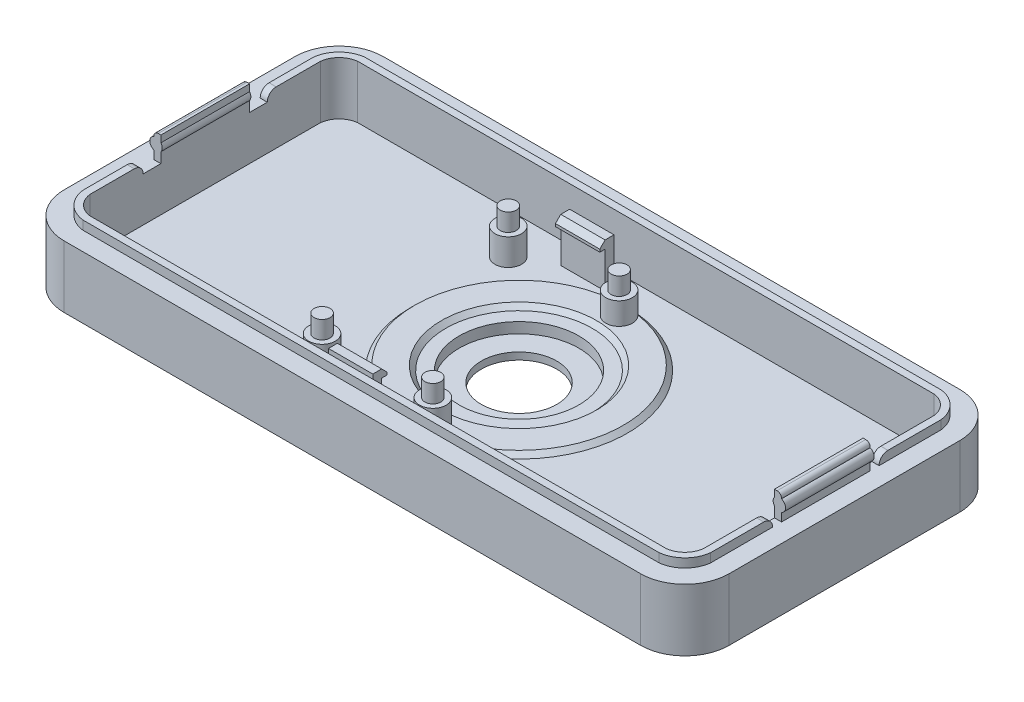
SolidWorks part; units mm, degrees
ref_plane "前视基准面" through (0, 0, 0) normal (0, 0, 1) x (1, 0, 0)
ref_plane "上视基准面" through (0, 0, 0) normal (0, 1, 0) x (1, 0, 0)
ref_plane "右视基准面" through (0, 0, 0) normal (1, 0, 0) x (0, 0, -1)
sketch "zero" plane through (0, 0, 0) normal (0, 1, 0) x (1, 0, 0)
  line L1 (-29.5, 15) -> (29.5, 15)
  line L2 (-32.5, 12) -> (-32.5, -12)
  line L3 (-29.5, -15) -> (29.5, -15)
  line L4 (32.5, 12) -> (32.5, -12)
  line L5 (-32.5, 15) -> (32.5, -15) construction
  line L6 (-32.5, -15) -> (32.5, 15) construction
  line L7 (-25.7, -15) -> (-14.5, -15)
  line L8 (-25.7, -15) -> (-25.7, -9.6569)
  line L9 (-25.7, -9.6569) -> (-14.5, -9.6569)
  line L10 (-14.5, -15) -> (-14.5, -9.6569)
  line L11 (5.2, -15) -> (12.7, -15)
  line L12 (5.2, -15) -> (5.2, -11)
  line L13 (5.2, -11) -> (12.7, -11)
  line L14 (12.7, -15) -> (12.7, -11)
  line L15 (17.8, -15) -> (25.3, -15)
  line L16 (17.8, -15) -> (17.8, -11)
  line L17 (17.8, -11) -> (25.3, -11)
  line L18 (25.3, -15) -> (25.3, -11)
  line L19 (-32.5, 7.7) -> (-19.5, 7.7)
  line L20 (-32.5, 7.7) -> (-32.5, -4.3)
  line L21 (-32.5, -4.3) -> (-19.5, -4.3)
  line L22 (-19.5, 7.7) -> (-19.5, -4.3)
  line L23 (-25.5, 14) -> (25.5, 14)
  line L24 (-25.5, 14) -> (-25.5, 8.8)
  line L25 (-25.5, 8.8) -> (25.5, 8.8)
  line L26 (25.5, 14) -> (25.5, 8.8)
  line L27 (-19.5, 7.2329) -> (-35.5, 7.2329)
  line L28 (-19.5, 7.2329) -> (-19.5, -3.7671)
  line L29 (-19.5, -3.7671) -> (-35.5, -3.7671)
  line L30 (-35.5, 7.2329) -> (-35.5, -3.7671)
  arc A0 (29.5, -15) -> (32.5, -12) centre (29.5, -12) ccw
  arc A1 (29.5, 15) -> (32.5, 12) centre (29.5, 12) cw
  arc A2 (-32.5, -12) -> (-29.5, -15) centre (-29.5, -12) ccw
  arc A3 (-29.5, 15) -> (-32.5, 12) centre (-29.5, 12) ccw
  circle A4 centre (-29, 11.4) radius 3
  circle A5 centre (-29, -11.5) radius 3
  circle A6 centre (29, 11.4) radius 3
  circle A7 centre (29, -11.5) radius 3
  circle A8 centre (-29, 11.4) radius 1.375
  circle A9 centre (-29, -11.5) radius 1.375
  circle A10 centre (29, -11.5) radius 1.375
  circle A11 centre (29, 11.4) radius 1.375
  point P0 (0, 0)
  dimension "D3" = 3
  dimension "D4" = 6
  dimension "D9" = 2.75
  dimension "D1" = 65
  dimension "D2" = 30
  dimension "D5" = 3.6
  dimension "D6" = 3.5
  dimension "D7" = 3.5
  dimension "D8" = 3.5
  dimension "D10" = 12
  dimension "D11" = 7.3
  dimension "D12" = 13
  dimension "D13" = 11.2
  dimension "D14" = 6.8
  dimension "D15" = 19.7
  dimension "D16" = 7.5
  dimension "D17" = 7.5
  dimension "D18" = 5.1
  dimension "D19" = 4
  dimension "D20" = 5.2
  dimension "D21" = 7
  dimension "D22" = 7
  dimension "D23" = 1
  dimension "D24" = 11
  dimension "D25" = 16
sketch "sugar" plane through (0, 0, 0) normal (0, 1, 0) x (1, 0, 0)
  line L1 (-29.5, 15) -> (29.5, 15)
  line L2 (-32.5, 12) -> (-32.5, -12)
  line L3 (-29.5, -15) -> (29.5, -15)
  line L4 (32.5, 12) -> (32.5, -12)
  line L5 (-32.5, 15) -> (32.5, -15) construction
  line L6 (-32.5, -15) -> (32.5, 15) construction
  line L7 (23.5, -11.5) -> (19.5, -11.5)
  line L8 (23.5, -11.5) -> (23.5, -13.9082)
  line L9 (23.5, -13.9082) -> (19.5, -13.9082)
  line L10 (19.5, -11.5) -> (19.5, -13.9082)
  line L11 (16, -11.0071) -> (8.5, -11.0071)
  line L12 (16, -11.0071) -> (16, -15)
  line L13 (16, -15) -> (8.5, -15)
  line L14 (8.5, -11.0071) -> (8.5, -15)
  line L15 (20.5, -13.9082) -> (22.5, -13.9082)
  line L16 (20.5, -13.9082) -> (20.5, -14.8173)
  line L17 (20.5, -14.8173) -> (22.5, -14.8173)
  line L18 (22.5, -13.9082) -> (22.5, -14.8173)
  arc A0 (29.5, 15) -> (32.5, 12) centre (29.5, 12) cw
  arc A1 (29.5, -15) -> (32.5, -12) centre (29.5, -12) ccw
  arc A2 (-32.5, -12) -> (-29.5, -15) centre (-29.5, -12) ccw
  arc A3 (-29.5, 15) -> (-32.5, 12) centre (-29.5, 12) ccw
  circle A4 centre (-29, 11.4) radius 3
  circle A5 centre (-29, 11.4) radius 1.375
  circle A6 centre (-29, -11.5) radius 3
  circle A7 centre (-29, -11.5) radius 1.375
  circle A8 centre (29, 11.4) radius 3
  circle A9 centre (29, 11.4) radius 1.375
  circle A10 centre (29, -11.5) radius 3
  circle A11 centre (29, -11.5) radius 1.375
  dimension "D3" = 3
  dimension "D1" = 65
  dimension "D2" = 30
  dimension "D4" = 9
  dimension "D5" = 4
  dimension "D6" = 3.5
  dimension "D7" = 7.5
  dimension "D8" = 2
  dimension "D9" = 1
sketch "case" plane through (0, 0, 0) normal (0, 1, 0) x (1, 0, 0)
  line L1 (-34.0422, 18) -> (30.9578, 18)
  line L2 (-39.0422, 13) -> (-39.0422, -13)
  line L3 (-34.0422, -18) -> (30.9578, -18)
  line L4 (35.9578, 13) -> (35.9578, -13)
  line L5 (-39.0422, 18) -> (35.9578, -18) construction
  line L6 (-39.0422, -18) -> (35.9578, 18) construction
  arc A0 (-39.0422, -13) -> (-34.0422, -18) centre (-34.0422, -13) ccw
  arc A1 (30.9578, -18) -> (35.9578, -13) centre (30.9578, -13) ccw
  arc A2 (30.9578, 18) -> (35.9578, 13) centre (30.9578, 13) cw
  arc A3 (-34.0422, 18) -> (-39.0422, 13) centre (-34.0422, 13) ccw
  point P0 (-1.5422, 0)
  point P3 (-1.5422, 0)
  dimension "D3" = 5
  dimension "D1" = 75
  dimension "D2" = 36
extrude "凸台-拉伸2" add sketch "case" along normal blind 7
sketch "草图2" plane through (0, 0, 0) normal (0, 1, 0) x (1, 0, 0)
  line L4 (-34.0422, -15.1) -> (30.9578, -15.1)
  line L5 (33.0578, -13) -> (33.0578, 13)
  line L6 (30.9578, 15.1) -> (-34.0422, 15.1)
  line L7 (-36.1422, 13) -> (-36.1422, -13)
  line L12 (33.8578, -13) -> (33.8578, 13)
  line L13 (30.9578, 15.9) -> (-34.0422, 15.9)
  line L14 (-36.9422, 13) -> (-36.9422, -13)
  line L15 (-34.0422, -15.9) -> (30.9578, -15.9)
  arc A4 (30.9578, -15.1) -> (33.0578, -13) centre (30.6746, -12.7168) ccw
  arc A5 (33.0578, 13) -> (30.9578, 15.1) centre (30.6746, 12.7168) ccw
  arc A6 (-34.0422, 15.1) -> (-36.1422, 13) centre (-33.759, 12.7168) ccw
  arc A7 (-36.1422, -13) -> (-34.0422, -15.1) centre (-33.759, -12.7168) ccw
  arc A12 (30.9578, -15.9) -> (33.8578, -13) centre (30.5796, -12.6217) ccw
  arc A13 (33.8578, 13) -> (30.9578, 15.9) centre (30.5796, 12.6217) ccw
  arc A14 (-34.0422, 15.9) -> (-36.9422, 13) centre (-33.6639, 12.6217) ccw
  arc A15 (-36.9422, -13) -> (-34.0422, -15.9) centre (-33.6639, -12.6217) ccw
ref_plane "基准面1" through (0, 7, 0) normal (0, 1, 0) x (1, 0, 0)
sketch "草图3" plane through (0, 7, 0) normal (0, 1, 0) x (1, 0, 0)
  line L4 (-34.0422, -15.1) -> (30.9578, -15.1)
  line L5 (33.0578, -13) -> (33.0578, 13)
  line L6 (30.9578, 15.1) -> (-34.0422, 15.1)
  line L7 (-36.1422, 13) -> (-36.1422, -13)
  line L8 (-34.0422, -15.1) -> (30.9578, -15.1)
  line L9 (33.0578, -13) -> (33.0578, 13)
  line L10 (30.9578, 15.1) -> (-34.0422, 15.1)
  line L11 (-36.1422, 13) -> (-36.1422, -13)
  line L12 (-36.9422, 13) -> (-36.9422, -13)
  line L13 (-34.0422, -15.9) -> (30.9578, -15.9)
  line L14 (33.8578, -13) -> (33.8578, 13)
  line L15 (30.9578, 15.9) -> (-34.0422, 15.9)
  line L16 (-36.9422, 13) -> (-36.9422, -13)
  line L17 (-34.0422, -15.9) -> (30.9578, -15.9)
  line L18 (33.8578, -13) -> (33.8578, 13)
  line L19 (30.9578, 15.9) -> (-34.0422, 15.9)
  arc A4 (30.9578, -15.1) -> (33.0578, -13) centre (30.6746, -12.7168) ccw
  arc A5 (33.0578, 13) -> (30.9578, 15.1) centre (30.6746, 12.7168) ccw
  arc A6 (-34.0422, 15.1) -> (-36.1422, 13) centre (-33.759, 12.7168) ccw
  arc A7 (-36.1422, -13) -> (-34.0422, -15.1) centre (-33.759, -12.7168) ccw
  arc A8 (30.9578, -15.1) -> (33.0578, -13) centre (30.6746, -12.7168) ccw
  arc A9 (33.0578, 13) -> (30.9578, 15.1) centre (30.6746, 12.7168) ccw
  arc A10 (-34.0422, 15.1) -> (-36.1422, 13) centre (-33.759, 12.7168) ccw
  arc A11 (-36.1422, -13) -> (-34.0422, -15.1) centre (-33.759, -12.7168) ccw
  arc A12 (-36.9422, -13) -> (-34.0422, -15.9) centre (-33.6639, -12.6217) ccw
  arc A13 (30.9578, -15.9) -> (33.8578, -13) centre (30.5796, -12.6217) ccw
  arc A14 (33.8578, 13) -> (30.9578, 15.9) centre (30.5796, 12.6217) ccw
  arc A15 (-34.0422, 15.9) -> (-36.9422, 13) centre (-33.6639, 12.6217) ccw
  arc A16 (-36.9422, -13) -> (-34.0422, -15.9) centre (-33.6639, -12.6217) ccw
  arc A17 (30.9578, -15.9) -> (33.8578, -13) centre (30.5796, -12.6217) ccw
  arc A18 (33.8578, 13) -> (30.9578, 15.9) centre (30.5796, 12.6217) ccw
  arc A19 (-34.0422, 15.9) -> (-36.9422, 13) centre (-33.6639, 12.6217) ccw
  dimension "D1" = 0
  dimension "D2" = 0
extrude "凸台-拉伸4" add sketch "草图3" along normal blind 1
ref_plane "基准面3" through (33.8578, 0, 0) normal (1, 0, 0) x (0, 0, -1)
sketch "草图7" plane through (0, 7, 0) normal (0, 1, 0) x (1, 0, 0)
  line L0 (-36.9422, 13) -> (-36.9422, -13) construction
  line L1 (-36.9422, 5) -> (-36.1422, 5)
  line L2 (-36.9422, 5) -> (-36.9422, -5)
  line L3 (-36.9422, -5) -> (-36.1422, -5)
  line L4 (-36.1422, 5) -> (-36.1422, -5)
  line L5 (-36.1422, 13) -> (-36.1422, -13) construction
  point P10 (-36.1422, 0)
  dimension "D1" = 5
  dimension "D2" = 10
extrude "凸台-拉伸8" add sketch "草图7" along normal blind 2.8
ref_plane "基准面5" through (0, 0, 5) normal (0, 0, 1) x (1, 0, 0)
sketch "草图8" plane through (0, 0, 5) normal (0, 0, 1) x (1, 0, 0)
  line L0 (-34.0422, 7) -> (-39.0422, 7) construction
  line L1 (-36.9422, 9.8) -> (-36.9422, 8) construction
  circle A0 centre (-36.6922, 8.6) radius 0.7
  dimension "D1" = 1.4
  dimension "D2" = 1.6
  dimension "D3" = 0.25
extrude "凸台-拉伸9" add sketch "草图8" against normal blind 10
fillet "圆角3" radius 0.5 1 edges at (-36.9422, 9.8, 0)
sketch "草图13" plane through (0, 8, 0) normal (0, 1, 0) x (1, 0, 0)
  line L0 (-36.9422, -5) -> (-36.9422, -13) construction
  line L1 (-36.1422, -5) -> (-36.9422, -5)
  line L2 (-36.1422, -5) -> (-36.1422, -7)
  line L3 (-36.1422, -7) -> (-36.9422, -7)
  line L4 (-36.9422, -5) -> (-36.9422, -7)
  line L5 (-36.9422, 13) -> (-36.9422, 5) construction
  line L6 (-36.1422, 5) -> (-36.9422, 5)
  line L7 (-36.1422, 5) -> (-36.1422, 7)
  line L8 (-36.1422, 7) -> (-36.9422, 7)
  line L9 (-36.9422, 5) -> (-36.9422, 7)
  dimension "D1" = 2
  dimension "D2" = 2
extrude "切除-拉伸2" cut sketch "草图13" against normal blind 1
sketch "草图15" plane through (0, 7, 0) normal (0, 1, 0) x (1, 0, 0)
  line L4 (-34.0422, -15.1) -> (30.9578, -15.1)
  line L5 (33.0578, -13) -> (33.0578, 13)
  line L6 (30.9578, 15.1) -> (-34.0422, 15.1)
  line L7 (-36.1422, 13) -> (-36.1422, -13)
  line L8 (-34.0422, -15.1) -> (30.9578, -15.1)
  line L9 (33.0578, -13) -> (33.0578, 13)
  line L10 (30.9578, 15.1) -> (-34.0422, 15.1)
  line L11 (-36.1422, 13) -> (-36.1422, -13)
  arc A4 (30.9578, -15.1) -> (33.0578, -13) centre (30.6746, -12.7168) ccw
  arc A5 (33.0578, 13) -> (30.9578, 15.1) centre (30.6746, 12.7168) ccw
  arc A6 (-34.0422, 15.1) -> (-36.1422, 13) centre (-33.759, 12.7168) ccw
  arc A7 (-36.1422, -13) -> (-34.0422, -15.1) centre (-33.759, -12.7168) ccw
  arc A8 (30.9578, -15.1) -> (33.0578, -13) centre (30.6746, -12.7168) ccw
  arc A9 (33.0578, 13) -> (30.9578, 15.1) centre (30.6746, 12.7168) ccw
  arc A10 (-34.0422, 15.1) -> (-36.1422, 13) centre (-33.759, 12.7168) ccw
  arc A11 (-36.1422, -13) -> (-34.0422, -15.1) centre (-33.759, -12.7168) ccw
  dimension "D1" = 0
extrude "切除-拉伸3" cut sketch "草图15" against normal blind 5
sketch "草图19" plane through (0, 2, 0) normal (0, 1, 0) x (1, 0, 0)
  line L1 (-39.0422, 13) -> (-39.0422, -13) construction
  circle A0 centre (-0.75, 0) radius 4.25
  dimension "D1" = 8.5
  dimension "D2" = 38.2922
extrude "切除-拉伸4" cut sketch "草图19" against normal blind 3
sketch "草图21" plane through (0, 2, 0) normal (0, 1, 0) x (1, 0, 0)
  line L0 (-34.0422, -15.1) -> (30.9578, -15.1) construction
  line L1 (30.9578, 15.1) -> (-34.0422, 15.1) construction
  line L3 (-36.1422, -7) -> (-36.1422, -13) construction
  line L4 (-36.1422, 13) -> (-36.1422, -13) construction
  line L5 (30.9578, 15.1) -> (-34.0422, 15.1) construction
  line L6 (-34.0422, -15.1) -> (30.9578, -15.1) construction
  circle A0 centre (-12.4653, 10.5) radius 1.5
  circle A1 centre (0.0347, 10.5) radius 1.5
  circle A2 centre (-12.4653, -10.5) radius 1.5
  circle A3 centre (0.0347, -10.5) radius 1.5
  dimension "D1" = 3
  dimension "D2" = 12.5
  dimension "D3" = 12.5
  dimension "D4" = 4.6
  dimension "D5" = 4.6
  dimension "D6" = 23.6769
  dimension "D7" = 23.6769
  dimension "D8" = 4.6
  dimension "D9" = 4.6
extrude "凸台-拉伸11" add sketch "草图21" along normal blind 3
sketch "草图22" plane through (0, 5, 0) normal (0, 1, 0) x (1, 0, 0)
  circle A0 centre (-12.4653, -10.5) radius 0.9
  circle A1 centre (0.0347, -10.5) radius 0.9
  circle A2 centre (-12.4653, 10.5) radius 0.9
  circle A3 centre (0.0347, 10.5) radius 0.9
  circle A4 centre (-12.4653, 10.5) radius 1.5 construction
  circle A5 centre (-12.4653, -10.5) radius 1.5 construction
  circle A6 centre (0.0347, -10.5) radius 1.5 construction
  circle A7 centre (0.0347, 10.5) radius 1.5 construction
  dimension "D1" = 1.8
extrude "凸台-拉伸12" add sketch "草图22" along normal blind 2
sketch "草图28" plane through (0, 2, 0) normal (0, 1, 0) x (1, 0, 0)
  line L0 (30.9578, 15.1) -> (-34.0422, 15.1) construction
  line L1 (-3.6422, -12.6) -> (-8.6422, -12.6)
  line L2 (-3.6422, -12.6) -> (-3.6422, -13.6)
  line L3 (-3.6422, -13.6) -> (-8.6422, -13.6)
  line L4 (-8.6422, -12.6) -> (-8.6422, -13.6)
  line L5 (-3.6422, 13.6) -> (-8.6422, 13.6)
  line L6 (-3.6422, 13.6) -> (-3.6422, 12.6)
  line L7 (-3.6422, 12.6) -> (-8.6422, 12.6)
  line L8 (-8.6422, 13.6) -> (-8.6422, 12.6)
  line L9 (-34.0422, -15.1) -> (30.9578, -15.1) construction
  line L10 (-36.1422, -7) -> (-36.1422, -13) construction
  dimension "D1" = 1
  dimension "D2" = 1.5
  dimension "D3" = 5
  dimension "D4" = 1.5
  dimension "D5" = 27.5
extrude "凸台-拉伸16" add sketch "草图28" along normal blind 5
fillet "圆角4" radius 1 2 edges at (-6.1422, 2, -13.6) (-6.1422, 2, 13.6)
sketch "草图29" plane through (0, 0, 12.6) normal (0, 0, -1) x (-1, 0, 0)
  line L0 (8.6422, 7) -> (8.6422, 2) construction
  line L1 (3.6422, 7) -> (8.6422, 7)
  line L2 (3.6422, 7) -> (3.6422, 6.1)
  line L3 (3.6422, 6.1) -> (8.6422, 6.1)
  line L4 (8.6422, 7) -> (8.6422, 6.1)
  dimension "D1" = 0.9
extrude "凸台-拉伸17" add sketch "草图29" along normal blind 0.6
sketch "草图30" plane through (0, 0, -12.6) normal (0, 0, 1) x (1, 0, 0)
  line L0 (-3.6422, 7) -> (-3.6422, 2) construction
  line L1 (-8.6422, 7) -> (-3.6422, 7)
  line L2 (-8.6422, 7) -> (-8.6422, 6.1)
  line L3 (-8.6422, 6.1) -> (-3.6422, 6.1)
  line L4 (-3.6422, 7) -> (-3.6422, 6.1)
  dimension "D1" = 0.9
extrude "凸台-拉伸18" add sketch "草图30" along normal blind 0.6
chamfer "倒角5" distance 0.6 angle 45 2 edges at (-6.1422, 7, -12) (-6.1422, 7, 12)
sketch "草图32" plane through (0, 0, 0) normal (0, 1, 0) x (1, 0, 0)
  line L75 (-14.6761, -9.5363) -> (-15.4836, -9.6938)
  line L76 (-12.4748, -8.5613) -> (-14.1869, -8.5613)
  line L77 (-12.4748, -7.6298) -> (-12.4748, -8.5613)
  line L78 (-15.4702, -7.6298) -> (-12.4748, -7.6298)
  line L79 (-15.4702, -8.3938) -> (-15.4702, -7.6298)
  line L80 (-14.9509, -8.4574) -> (-15.4702, -8.3938)
  line L81 (-14.9509, -8.4776) -> (-14.9509, -8.4574)
  line L82 (-13.8452, -6.0752) -> (-13.366, -6.0752)
  line L83 (-12.4748, -7.0133) -> (-14.1769, -7.0133)
  line L84 (-12.4748, -6.2494) -> (-12.4748, -7.0133)
  line L85 (-12.7763, -6.1824) -> (-12.4748, -6.2494)
  line L86 (-12.7763, -6.1589) -> (-12.7763, -6.1824)
  line L87 (-15.1519, -4.5104) -> (-14.5354, -4.8388)
  line L88 (-12.3475, -2.6743) -> (-12.3475, -2.9592)
  line L89 (-12.5853, -1.763) -> (-12.5586, -1.763)
  line L90 (-13.681, -1.8199) -> (-13.6609, -1.8199)
  line L91 (-15.4702, -4.2424) -> (-15.4702, -3.1434)
  line L92 (-14.7934, -4.2424) -> (-15.4702, -4.2424)
  line L93 (-14.7934, -3.78) -> (-14.7934, -4.2424)
  line L94 (-13.0645, -3.1367) -> (-13.0645, -2.6643)
  line L95 (-15.4702, -0.8717) -> (-15.4702, 0.0664)
  line L96 (-12.4748, -0.8717) -> (-15.4702, -0.8717)
  line L97 (-12.4748, -0.1078) -> (-12.4748, -0.8717)
  line L98 (-12.8869, -0.0408) -> (-12.4748, -0.1078)
  line L99 (-12.8869, -0.0207) -> (-12.8869, -0.0408)
  line L100 (-15.4702, 1.849) -> (-13.6173, 1.849)
  line L101 (-15.4702, 0.9141) -> (-15.4702, 1.849)
  line L102 (-13.7346, 0.9141) -> (-15.4702, 0.9141)
  line L103 (-15.4702, 0.0664) -> (-13.5068, 0.0664)
  line L104 (-13.614, 4.7204) -> (-12.964, 5.2531)
  line L105 (-14.207, 4.3083) -> (-13.9959, 3.809)
  line L106 (-15.3596, 2.8776) -> (-15.9493, 2.4085)
  line L107 (-14.7029, 3.0686) -> (-14.8973, 3.5577)
  line L108 (-15.3362, 5.8361) -> (-15.3362, 6.3153)
  line L109 (-12.4748, 5.8361) -> (-15.3362, 5.8361)
  line L110 (-12.4748, 6.3153) -> (-12.4748, 5.8361)
  line L111 (-15.3362, 6.3153) -> (-12.4748, 6.3153)
  line L112 (-15.9393, 9.0091) -> (-15.9393, 8.4529)
  line L113 (-14.4014, 9.0091) -> (-15.9393, 9.0091)
  line L114 (-14.4014, 8.4328) -> (-14.4014, 9.0091)
  line L115 (-14.006, 9.0091) -> (-14.006, 8.3692)
  line L116 (-12.4748, 9.0091) -> (-14.006, 9.0091)
  line L117 (-12.4748, 9.4984) -> (-12.4748, 9.0091)
  line L118 (-16.3346, 9.4984) -> (-12.4748, 9.4984)
  line L119 (-16.3346, 8.396) -> (-16.3346, 9.4984)
  spline S0 degree 3 poles (-15.4836, -9.6938) (-15.5205, -9.61) (-15.5439, -9.5095) (-15.5439, -9.3319) knots 10 10 10 10 11 11 11 11
  spline S1 degree 3 poles (-14.723, -9.208) (-14.723, -9.342) (-14.7029, -9.4291) (-14.6761, -9.5363) knots 8 8 8 8 9 9 9 9
  spline S2 degree 3 poles (-14.1869, -8.5613) (-14.5823, -8.7188) (-14.723, -8.9869) (-14.723, -9.208) knots 7 7 7 7 8 8 8 8
  spline S3 degree 3 poles (-15.5439, -9.3319) (-15.5439, -9.0304) (-15.3496, -8.6987) (-14.9509, -8.4776) knots 0 0 0 0 1 1 1 1
  spline S4 degree 3 poles (-13.3861, -5.3012) (-13.5972, -5.3012) (-13.7648, -5.4922) (-13.8452, -6.0752) knots 2 2 2 2 3 3 3 3
  spline S5 degree 3 poles (-13.1282, -5.6229) (-13.1282, -5.4285) (-13.2119, -5.3012) (-13.3861, -5.3012) knots 1 1 1 1 2 2 2 2
  spline S6 degree 3 poles (-13.366, -6.0752) (-13.2186, -5.9378) (-13.1282, -5.8138) (-13.1282, -5.6229) knots 0 0 0 0 1 1 1 1
  spline S7 degree 3 poles (-14.1769, -7.0133) (-15.1151, -7.0133) (-15.5439, -6.5744) (-15.5439, -5.8004) knots 11 11 11 11 12 12 12 12
  spline S8 degree 3 poles (-12.4011, -5.3012) (-12.4011, -5.6329) (-12.5552, -5.911) (-12.7763, -6.1589) knots 6 6 6 6 7 7 7 7
  spline S9 degree 3 poles (-13.3124, -4.4099) (-12.8132, -4.4099) (-12.4011, -4.7483) (-12.4011, -5.3012) knots 5 5 5 5 6 6 6 6
  spline S10 degree 3 poles (-14.4148, -6.0752) (-14.2874, -4.9058) (-13.9457, -4.4099) (-13.3124, -4.4099) knots 4 4 4 4 5 5 5 5
  spline S11 degree 3 poles (-14.7967, -5.6229) (-14.7967, -5.9277) (-14.656, -6.0551) (-14.4148, -6.0752) knots 3 3 3 3 4 4 4 4
  spline S12 degree 3 poles (-14.5354, -4.8388) (-14.7029, -5.137) (-14.7967, -5.385) (-14.7967, -5.6229) knots 2 2 2 2 3 3 3 3
  spline S13 degree 3 poles (-15.5439, -5.8004) (-15.5439, -5.3347) (-15.3864, -4.9058) (-15.1519, -4.5104) knots 0 0 0 0 1 1 1 1
  spline S14 degree 3 poles (-12.133, -3.3947) (-11.942, -3.3947) (-11.8013, -3.1267) (-11.8013, -2.7413) knots 5 5 5 5 6 6 6 6
  spline S15 degree 3 poles (-12.3475, -2.9592) (-12.3475, -3.2372) (-12.3106, -3.3947) (-12.133, -3.3947) knots 4 4 4 4 5 5 5 5
  spline S16 degree 3 poles (-12.3843, -2.2454) (-12.3575, -2.3426) (-12.3475, -2.4566) (-12.3475, -2.6743) knots 2 2 2 2 3 3 3 3
  spline S17 degree 3 poles (-12.1163, -2.1047) (-12.2168, -2.1047) (-12.3006, -2.1516) (-12.3843, -2.2454) knots 1 1 1 1 2 2 2 2
  spline S18 degree 3 poles (-11.8013, -2.7413) (-11.8013, -2.356) (-11.9052, -2.1047) (-12.1163, -2.1047) knots 0 0 0 0 1 1 1 1
  spline S19 degree 3 poles (-14.9174, -2.6676) (-14.9174, -2.8888) (-14.7599, -3.0462) (-14.455, -3.0462) (-14.1434, -3.0462) (-13.9859, -2.8888) (-13.9859, -2.6676) knots 0 0 0 0 1 1 1 2 2 2 2
  spline S20 degree 3 poles (-13.9859, -2.6676) (-13.9859, -2.4532) (-14.1434, -2.289) (-14.455, -2.289) (-14.7599, -2.289) (-14.9174, -2.4532) (-14.9174, -2.6676) knots 2 2 2 2 3 3 3 4 4 4 4
  spline S21 degree 3 poles (-12.2972, -4.2893) (-12.84, -4.2893) (-13.0645, -3.8739) (-13.0645, -3.1367) knots 19 19 19 19 20 20 20 20
  spline S22 degree 3 poles (-11.215, -2.5939) (-11.215, -3.6359) (-11.6639, -4.2893) (-12.2972, -4.2893) knots 18 18 18 18 19 19 19 19
  spline S23 degree 3 poles (-11.9688, -1.3374) (-11.4328, -1.3374) (-11.215, -1.9037) (-11.215, -2.5939) knots 17 17 17 17 18 18 18 18
  spline S24 degree 3 poles (-12.5586, -1.763) (-12.4178, -1.4849) (-12.2168, -1.3374) (-11.9688, -1.3374) knots 16 16 16 16 17 17 17 17
  spline S25 degree 3 poles (-13.1013, -1.4882) (-12.8501, -1.4882) (-12.6926, -1.6055) (-12.5853, -1.763) knots 14 14 14 14 15 15 15 15
  spline S26 degree 3 poles (-13.6609, -1.8199) (-13.5235, -1.6256) (-13.3124, -1.4882) (-13.1013, -1.4882) knots 13 13 13 13 14 14 14 14
  spline S27 degree 3 poles (-14.455, -1.4145) (-14.1065, -1.4145) (-13.8284, -1.6089) (-13.681, -1.8199) knots 11 11 11 11 12 12 12 12
  spline S28 degree 3 poles (-15.5439, -2.6676) (-15.5439, -2.021) (-15.1888, -1.4145) (-14.455, -1.4145) knots 10 10 10 10 11 11 11 11
  spline S86 degree 3 poles (-15.4702, -3.1434) (-15.5205, -3.006) (-15.5439, -2.8419) (-15.5439, -2.6676) knots 9 9 9 9 10 10 10 10
  spline S87 degree 3 poles (-14.4282, -3.8638) (-14.5723, -3.8638) (-14.7096, -3.8269) (-14.7934, -3.78) knots 5 5 5 5 6 6 6 6
  spline S88 degree 3 poles (-13.423, -2.6676) (-13.423, -3.331) (-13.7279, -3.8638) (-14.4282, -3.8638) knots 4 4 4 4 5 5 5 5
  spline S89 degree 3 poles (-13.4766, -2.3158) (-13.4398, -2.4465) (-13.423, -2.5671) (-13.423, -2.6676) knots 3 3 3 3 4 4 4 4
  spline S90 degree 3 poles (-13.2655, -2.222) (-13.366, -2.222) (-13.4129, -2.2454) (-13.4766, -2.3158) knots 2 2 2 2 3 3 3 3
  spline S91 degree 3 poles (-13.0645, -2.6643) (-13.0645, -2.3426) (-13.1282, -2.222) (-13.2655, -2.222) knots 1 1 1 1 2 2 2 2
  spline S92 degree 3 poles (-12.4011, 0.9175) (-12.4011, 0.5087) (-12.5921, 0.2272) (-12.8869, -0.0207) knots 7 7 7 7 8 8 8 8
  spline S93 degree 3 poles (-13.6173, 1.849) (-12.8702, 1.849) (-12.4011, 1.5708) (-12.4011, 0.9175) knots 6 6 6 6 7 7 7 7
  spline S94 degree 3 poles (-13.2019, 0.5657) (-13.2019, 0.8036) (-13.3191, 0.9141) (-13.7346, 0.9141) knots 2 2 2 2 3 3 3 3
  spline S95 degree 3 poles (-13.5068, 0.0664) (-13.2856, 0.2239) (-13.2019, 0.3546) (-13.2019, 0.5657) knots 1 1 1 1 2 2 2 2
  spline S96 degree 3 poles (-13.6274, 2.2913) (-14.1802, 2.2913) (-14.5086, 2.5827) (-14.7029, 3.0686) knots 15 15 15 15 16 16 16 16
  spline S97 degree 3 poles (-12.4011, 3.789) (-12.4011, 2.8407) (-12.974, 2.2913) (-13.6274, 2.2913) knots 14 14 14 14 15 15 15 15
  spline S98 degree 3 poles (-12.964, 5.2531) (-12.5921, 4.8477) (-12.4011, 4.2983) (-12.4011, 3.789) knots 13 13 13 13 14 14 14 14
  spline S99 degree 3 poles (-13.2119, 3.7688) (-13.2119, 4.0771) (-13.3761, 4.4423) (-13.614, 4.7204) knots 11 11 11 11 12 12 12 12
  spline S100 degree 3 poles (-13.5537, 3.2562) (-13.3426, 3.2562) (-13.2119, 3.4204) (-13.2119, 3.7688) knots 10 10 10 10 11 11 11 11
  spline S101 degree 3 poles (-13.9959, 3.809) (-13.8552, 3.474) (-13.7815, 3.2562) (-13.5537, 3.2562) knots 9 9 9 9 10 10 10 10
  spline S102 degree 3 poles (-15.2826, 5.1057) (-14.713, 5.1057) (-14.3712, 4.7204) (-14.207, 4.3083) knots 7 7 7 7 8 8 8 8
  spline S103 degree 3 poles (-16.4687, 3.6817) (-16.4687, 4.516) (-15.9393, 5.1057) (-15.2826, 5.1057) knots 6 6 6 6 7 7 7 7
  spline S104 degree 3 poles (-15.9493, 2.4085) (-16.2944, 2.7502) (-16.4687, 3.2294) (-16.4687, 3.6817) knots 5 5 5 5 6 6 6 6
  spline S105 degree 3 poles (-15.6612, 3.6817) (-15.6612, 3.3768) (-15.5573, 3.1356) (-15.3596, 2.8776) knots 3 3 3 3 4 4 4 4
  spline S106 degree 3 poles (-15.3362, 4.1508) (-15.5439, 4.1508) (-15.6612, 3.9732) (-15.6612, 3.6817) knots 2 2 2 2 3 3 3 3
  spline S107 degree 3 poles (-14.8973, 3.5577) (-15.0346, 3.9029) (-15.1184, 4.1508) (-15.3362, 4.1508) knots 1 1 1 1 2 2 2 2
  spline S108 degree 3 poles (-16.5457, 6.074) (-16.5457, 6.265) (-16.4318, 6.4057) (-16.2341, 6.4057) (-16.0566, 6.4057) (-15.9259, 6.265) (-15.9259, 6.074) knots 0 0 0 0 1 1 1 2 2 2 2
  spline S109 degree 3 poles (-15.9259, 6.074) (-15.9259, 5.8831) (-16.0566, 5.7423) (-16.2341, 5.7423) (-16.4318, 5.7423) (-16.5457, 5.8831) (-16.5457, 6.074) knots 2 2 2 2 3 3 3 4 4 4 4
  spline S110 degree 3 poles (-15.2022, 7.4343) (-14.6493, 7.4343) (-14.4014, 7.7527) (-14.4014, 8.4328) knots 4 4 4 4 5 5 5 5
  spline S111 degree 3 poles (-15.9393, 8.4529) (-15.9393, 7.7761) (-15.7617, 7.4343) (-15.2022, 7.4343) knots 3 3 3 3 4 4 4 4
  spline S112 degree 3 poles (-15.2022, 6.9485) (-16.0465, 6.9485) (-16.3346, 7.5282) (-16.3346, 8.396) knots 6 6 6 6 7 7 7 7
  spline S113 degree 3 poles (-14.006, 8.3692) (-14.006, 7.5282) (-14.388, 6.9485) (-15.2022, 6.9485) knots 5 5 5 5 6 6 6 6
sketch "草图33" plane through (0, 0, 0) normal (0, -1, 0) x (1, 0, 0)
  line L0 (31.4528, 12.8823) -> (31.1283, 13.0694)
  line L1 (31.1283, 13.0694) -> (29.4447, 14.0408)
  line L2 (29.4447, 14.0408) -> (29.1201, 14.2301)
  line L3 (28.4395, 14.2301) -> (28.1149, 14.0408)
  line L4 (28.1149, 14.0408) -> (26.4313, 13.0694)
  line L5 (26.4313, 13.0694) -> (26.1067, 12.8823)
  line L6 (25.7664, 12.2941) -> (25.7664, 9.5985)
  line L7 (26.1067, 9.0102) -> (26.4313, 8.8231)
  line L8 (26.4313, 8.8231) -> (28.1149, 7.8517)
  line L9 (28.1149, 7.8517) -> (28.4395, 7.6624)
  line L10 (29.1201, 7.6624) -> (29.4447, 7.8517)
  line L11 (29.4447, 7.8517) -> (31.1283, 8.8231)
  line L12 (31.1283, 8.8231) -> (31.4528, 9.0102)
  line L13 (31.7932, 9.5985) -> (31.7932, 12.2941)
  line L14 (26.5395, 12.6141) -> (28.622, 13.8177)
  line L15 (28.9398, 13.8177) -> (31.0111, 12.6118)
  line L16 (31.0134, 12.3346) -> (29.0007, 11.1311)
  line L17 (29.625, 9.0913) -> (29.3906, 8.9606)
  line L18 (29.368, 8.9223) -> (29.368, 8.2461)
  line L19 (29.3455, 8.2078) -> (28.9083, 7.9599)
  line L20 (28.8429, 7.9982) -> (28.8429, 10.0853)
  line L21 (28.8654, 10.1236) -> (29.6092, 10.5451)
  line L22 (31.1689, 9.2311) -> (30.7361, 8.9854)
  line L23 (30.6708, 9.0237) -> (30.6708, 10.0177)
  line L24 (30.6933, 10.056) -> (31.126, 10.2994)
  line L25 (31.1914, 10.2611) -> (31.1914, 9.2694)
  line L26 (29.5979, 9.4925) -> (29.3906, 9.3888)
  line L27 (29.368, 9.4362) -> (29.368, 9.9681)
  line L28 (29.3906, 10.0064) -> (29.5844, 10.1146)
  line L29 (29.3906, 9.3888) -> (29.3906, 8.9606)
  line L30 (29.368, 9.4362) -> (29.368, 8.9223)
  spline S0 degree 3 poles (29.1201, 14.2301) (29.0142, 14.2887) (28.897, 14.3203) (28.7798, 14.3203) knots 3 3 3 3 4 4 4 4
  spline S1 degree 3 poles (28.7798, 14.3203) (28.6626, 14.3203) (28.5454, 14.2887) (28.4395, 14.2301) knots 4 4 4 4 5 5 5 5
  spline S2 degree 3 poles (26.1067, 12.8823) (25.8971, 12.7606) (25.7664, 12.5352) (25.7664, 12.2941) knots 8 8 8 8 9 9 9 9
  spline S3 degree 3 poles (25.7664, 9.5985) (25.7664, 9.355) (25.8971, 9.1319) (26.1067, 9.0102) knots 10 10 10 10 11 11 11 11
  spline S4 degree 3 poles (28.4395, 7.6624) (28.5454, 7.6015) (28.6626, 7.5722) (28.7798, 7.5722) knots 14 14 14 14 15 15 15 15
  spline S5 degree 3 poles (28.7798, 7.5722) (28.897, 7.5722) (29.0142, 7.6015) (29.1201, 7.6624) knots 15 15 15 15 16 16 16 16
  spline S6 degree 3 poles (31.4528, 9.0102) (31.6647, 9.1319) (31.7932, 9.355) (31.7932, 9.5985) knots 19 19 19 19 20 20 20 20
  spline S7 degree 3 poles (31.7932, 12.2941) (31.7932, 12.5352) (31.6647, 12.7606) (31.4528, 12.8823) knots 21 21 21 21 22 22 22 22
  spline S8 degree 2 poles (28.5612, 11.1311) (26.5237, 12.3076) (26.5192, 12.3098) knots 0 0 0 1 1 1
  spline S9 degree 3 poles (26.5192, 12.3098) (26.4133, 12.3865) (26.4245, 12.5487) (26.5395, 12.6141) knots 1 1 1 1 2 2 2 2
  spline S10 degree 3 poles (28.622, 13.8177) (28.719, 13.874) (28.8407, 13.874) (28.9398, 13.8177) knots 3 3 3 3 4 4 4 4
  spline S11 degree 3 poles (31.0111, 12.6118) (31.117, 12.551) (31.1193, 12.3977) (31.0134, 12.3346) knots 5 5 5 5 6 6 6 6
  spline S12 degree 3 poles (29.0007, 11.1311) (28.8654, 11.0522) (28.6964, 11.0522) (28.5612, 11.1311) knots 7 7 7 7 8 8 8 8
  spline S13 degree 3 poles (29.368, 8.2461) (29.368, 8.2304) (29.3613, 8.2168) (29.3455, 8.2078) knots 3 3 3 3 4 4 4 4
  spline S14 degree 3 poles (28.9083, 7.9599) (28.879, 7.9441) (28.8429, 7.9644) (28.8429, 7.9982) knots 5 5 5 5 6 6 6 6
  spline S15 degree 3 poles (28.8429, 10.0853) (28.8429, 10.1011) (28.8497, 10.1168) (28.8654, 10.1236) knots 7 7 7 7 8 8 8 8
  spline S16 degree 3 poles (29.6092, 10.5451) (30.0915, 10.8178) (30.4904, 10.8719) (30.4904, 10.331) knots 9 9 9 9 10 10 10 10
  spline S17 degree 3 poles (30.4904, 10.331) (30.4904, 9.8103) (30.087, 9.3528) (29.625, 9.0913) knots 10 10 10 10 11 11 11 11
  spline S18 degree 3 poles (31.1914, 9.2694) (31.1914, 9.2536) (31.1824, 9.2378) (31.1689, 9.2311) knots 0 0 0 0 1 1 1 1
  spline S19 degree 3 poles (30.7361, 8.9854) (30.7068, 8.9696) (30.6708, 8.9899) (30.6708, 9.0237) knots 2 2 2 2 3 3 3 3
  spline S20 degree 3 poles (30.6708, 10.0177) (30.6708, 10.0334) (30.6798, 10.047) (30.6933, 10.056) knots 4 4 4 4 5 5 5 5
  spline S21 degree 3 poles (31.126, 10.2994) (31.1553, 10.3152) (31.1914, 10.2949) (31.1914, 10.2611) knots 6 6 6 6 7 7 7 7
  spline S22 degree 3 poles (30.9322, 10.9598) (31.1058, 11.059) (31.2297, 11.0161) (31.2297, 10.8584) (31.2297, 10.7028) (31.1058, 10.5203) (30.9322, 10.4234) knots 2 2 2 2 3 3 3 4 4 4 4
  spline S23 degree 3 poles (30.9322, 10.4234) (30.7564, 10.3219) (30.6325, 10.3648) (30.6325, 10.5203) (30.6325, 10.6803) (30.7564, 10.8606) (30.9322, 10.9598) knots 0 0 0 0 1 1 1 2 2 2 2
  spline S24 degree 3 poles (29.9766, 10.0402) (29.9766, 9.8261) (29.8549, 9.6368) (29.5979, 9.4925) knots 0 0 0 0 1 1 1 1
  spline S25 degree 3 poles (29.368, 9.9681) (29.368, 9.9839) (29.3771, 9.9996) (29.3906, 10.0064) knots 4 4 4 4 5 5 5 5
  spline S26 degree 3 poles (29.5844, 10.1146) (29.8369, 10.2588) (29.9766, 10.2611) (29.9766, 10.0402) knots 6 6 6 6 7 7 7 7
extrude "切除-拉伸5" cut sketch "草图33" against normal blind 0.5
sketch "草图34" plane through (0, 8, 0) normal (0, 1, 0) x (1, 0, 0)
  line L0 (33.8578, -13) -> (33.8578, 13) construction
  line L1 (33.8578, -6) -> (33.0578, -6)
  line L2 (33.8578, -6) -> (33.8578, 6)
  line L3 (33.8578, 6) -> (33.0578, 6)
  line L4 (33.0578, -6) -> (33.0578, 6)
  line L5 (33.0578, -13) -> (33.0578, 13) construction
  line L6 (35.9578, -13) -> (35.9578, 13) construction
  point P8 (33.0578, 0)
  point P11 (35.9578, 0)
  dimension "D1" = 12
extrude "切除-拉伸6" cut sketch "草图34" against normal blind 1
sketch "草图35" plane through (0, 7, 0) normal (0, 1, 0) x (1, 0, 0)
  line L0 (33.0578, 6) -> (33.0578, -6) construction
  line L1 (33.0578, -5) -> (33.8578, -5)
  line L2 (33.0578, -5) -> (33.0578, 5)
  line L3 (33.0578, 5) -> (33.8578, 5)
  line L4 (33.8578, -5) -> (33.8578, 5)
  line L5 (35.9578, -13) -> (35.9578, 13) construction
  point P6 (33.8578, 0)
  point P9 (35.9578, 0)
  dimension "D1" = 10
  dimension "D2" = 0.8
extrude "凸台-拉伸19" add sketch "草图35" along normal blind 2.8
sketch "草图36" plane through (0, 0, -5) normal (0, 0, -1) x (-1, 0, 0)
  line L0 (-30.9578, 7) -> (-35.9578, 7) construction
  line L1 (-33.8578, 9.8) -> (-33.8578, 7) construction
  circle A0 centre (-33.6096, 8.6) radius 0.7
  dimension "D1" = 1.4
  dimension "D2" = 1.6
  dimension "D3" = 0.2482
extrude "凸台-拉伸20" add sketch "草图36" against normal blind 10
fillet "圆角5" radius 0.5 1 edges at (33.8578, 9.8, 0)
fillet "圆角6" radius 1 4 edges at (33.4578, 8, -6) (33.4578, 8, 6) (-36.5422, 8, 7) (-36.5422, 8, -7)
sketch "草图37" plane through (0, 0, 0) normal (0, -1, 0) x (1, 0, 0)
  circle A0 centre (-0.75, 0) radius 11.75
  circle A1 centre (-0.75, 0) radius 4.25 construction
  circle A2 centre (-0.75, 0) radius 9.25
  dimension "D1" = 23.5
  dimension "D2" = 18.5
extrude "切除-拉伸7" cut sketch "草图37" against normal blind 1.5
chamfer "倒角6" distance 1.2 angle 45 1 edges at (-0.75, 0, -9.25)
chamfer "倒角7" distance 0.5 angle 45 1 edges at (-0.75, 0, -11.75)
sketch "草图38" plane through (0, 2, 0) normal (0, 1, 0) x (1, 0, 0)
  circle A1 centre (-0.75, 0) radius 8.25
  circle A2 centre (-0.75, 0) radius 12.25
  dimension "D2" = 4
  dimension "D1" = 24.5
extrude "凸台-拉伸21" add sketch "草图38" along normal blind 0.5
chamfer "倒角8" distance 0.5 angle 45 2 edges at (-0.75, 2.5, 8.25) (-0.75, 2.5, 12.25)
ref_plane "基准面7" through (-36.9422, 0, 0) normal (-1, 0, 0) x (0, 0, 1)
ref_plane "基准面8" through (0, 0, 0) normal (0, -1, 0) x (-1, 0, 0)
sketch "草图12" plane through (0, 0, 0) normal (0, -1, 0) x (-1, 0, 0)
  line L76 (34.0422, -18) -> (-30.9578, -18) construction
  line L78 (39.0422, 13) -> (39.0422, -13) construction
  line B0 (-8.1993, 5.026) -> (-9.0198, 5.499)
  line B1 (-9.0198, 5.499) -> (-13.2767, 7.9551)
  line B2 (-13.2767, 7.9551) -> (-14.0973, 8.4339)
  line B3 (-15.8183, 8.4339) -> (-16.6389, 7.9551)
  line B4 (-16.6389, 7.9551) -> (-20.8958, 5.499)
  line B5 (-20.8958, 5.499) -> (-21.7165, 5.026)
  line B6 (-22.577, 3.5387) -> (-22.577, -3.2769)
  line B7 (-21.7165, -4.7643) -> (-20.8958, -5.2373)
  line B8 (-20.8958, -5.2373) -> (-16.6389, -7.6934)
  line B9 (-16.6389, -7.6934) -> (-15.8183, -8.172)
  line B10 (-14.0973, -8.172) -> (-13.2767, -7.6934)
  line B11 (-13.2767, -7.6934) -> (-9.0198, -5.2373)
  line B12 (-9.0198, -5.2373) -> (-8.1993, -4.7643)
  line B13 (-7.3388, -3.2769) -> (-7.3388, 3.5387)
  line B14 (-20.6223, 4.3479) -> (-15.3568, 7.391)
  line B15 (-14.5532, 7.391) -> (-9.3162, 4.3422)
  line B16 (-9.3105, 3.6413) -> (-14.3993, 0.5982)
  line B17 (-12.8208, -4.5591) -> (-13.4135, -4.8896)
  line B18 (-13.4705, -4.9865) -> (-13.4705, -6.6961)
  line B19 (-13.5274, -6.793) -> (-14.633, -7.4198)
  line B20 (-14.7983, -7.3229) -> (-14.7983, -2.046)
  line B21 (-14.7413, -1.9491) -> (-12.8607, -0.8835)
  line B22 (-8.9173, -4.2058) -> (-10.0114, -4.8269)
  line B23 (-10.1767, -4.7301) -> (-10.1767, -2.2169)
  line B24 (-10.1197, -2.1201) -> (-9.0256, -1.5046)
  line B25 (-8.8603, -1.6015) -> (-8.8603, -4.1089)
  line B26 (-12.8893, -3.5447) -> (-13.4135, -3.8069)
  line B27 (-13.4705, -3.6872) -> (-13.4705, -2.3423)
  line B28 (-13.4135, -2.2455) -> (-12.9234, -1.9719)
  line B29 (-3.344, 3.06) -> (-5.2189, 3.06)
  line B30 (-5.2189, 3.06) -> (-5.2189, -3.5048)
  line B31 (-5.2189, -3.5048) -> (-4.3868, -3.5048)
  line B32 (-4.3868, -3.5048) -> (-4.3868, -0.9005)
  line B33 (-4.3868, -0.9005) -> (-3.2984, -0.9005)
  line B34 (-3.4066, -0.2281) -> (-4.3868, -0.2281)
  line B35 (-4.3868, -0.2281) -> (-4.3868, 2.3876)
  line B36 (-4.3868, 2.3876) -> (-3.4408, 2.3876)
  line B37 (0.1948, 1.3618) -> (0.1948, -3.5048)
  line B38 (0.1948, -3.5048) -> (1.0098, -3.5048)
  line B39 (1.0098, -3.5048) -> (1.0098, 1.3618)
  line B40 (1.0098, 1.3618) -> (0.1948, 1.3618)
  line B41 (5.7169, 0.2847) -> (4.8849, 0.6153)
  line B42 (6.0417, 1.4017) -> (6.8396, 2.4047)
  line B43 (3.6084, -0.5586) -> (4.4575, -0.9177)
  line B44 (2.9074, -1.5673) -> (2.0014, -2.6729)
  line B45 (10.8229, 1.5898) -> (10.8229, -1.7497)
  line B46 (9.3811, -1.3621) -> (9.3811, 1.5898)
  line B47 (9.3811, 1.5898) -> (7.7912, 1.5898)
  line B48 (7.7912, 1.5898) -> (7.7912, -1.5616)
  line B49 (10.9711, -2.8039) -> (11.0052, -2.8039)
  line B50 (11.0052, -2.8039) -> (11.1193, -3.5048)
  line B51 (11.1193, -3.5048) -> (12.4185, -3.5048)
  line B52 (12.4185, -3.5048) -> (12.4185, 1.5898)
  line B53 (12.4185, 1.5898) -> (10.8229, 1.5898)
  line B54 (16.2708, -2.5019) -> (15.4673, -2.5019)
  line B55 (17.365, 0.4386) -> (18.1513, 0.4386)
  line B56 (18.1513, 0.4386) -> (18.1513, 1.5898)
  line B57 (18.1513, 1.5898) -> (16.2822, 1.5898)
  line B58 (14.0312, -1.4533) -> (14.0312, -1.4875)
  line B59 (13.9344, -3.3168) -> (13.9344, -3.3624)
  line B60 (15.4844, -3.7214) -> (15.9688, -3.7214)
  line B61 (18.6072, 1.0484) -> (19.1657, -0.0002)
  line B62 (21.411, -2.992) -> (21.4508, -2.992)
  line B63 (21.4508, -2.992) -> (21.5648, -3.5048)
  line B64 (21.5648, -3.5048) -> (22.8641, -3.5048)
  line B65 (22.8641, -3.5048) -> (22.8641, -0.6099)
  line B66 (21.2685, -1.1741) -> (21.2685, -1.989)
  line B67 (25.3545, 0.7065) -> (25.3203, 0.7065)
  line B68 (25.3203, 0.7065) -> (25.212, 1.5898)
  line B69 (25.212, 1.5898) -> (23.9127, 1.5898)
  line B70 (23.9127, 1.5898) -> (23.9127, -3.5048)
  line B71 (23.9127, -3.5048) -> (25.4969, -3.5048)
  line B72 (25.4969, -3.5048) -> (25.4969, -0.5928)
  line B73 (27.1552, 0.2392) -> (27.423, 1.6125)
  line B74 (-13.4135, -3.8069) -> (-13.4135, -4.8896)
  line B75 (-13.4705, -3.6872) -> (-13.4705, -4.9865)
  spline B76 degree 3 poles (-14.0973, 8.4339) (-14.3652, 8.582) (-14.6615, 8.6618) (-14.9578, 8.6618) knots 3 3 3 3 4 4 4 4
  spline B77 degree 3 poles (-14.9578, 8.6618) (-15.2541, 8.6618) (-15.5505, 8.582) (-15.8183, 8.4339) knots 4 4 4 4 5 5 5 5
  spline B78 degree 3 poles (-21.7165, 5.026) (-22.2464, 4.7183) (-22.577, 4.1485) (-22.577, 3.5387) knots 8 8 8 8 9 9 9 9
  spline B79 degree 3 poles (-22.577, -3.2769) (-22.577, -3.8923) (-22.2464, -4.4565) (-21.7165, -4.7643) knots 10 10 10 10 11 11 11 11
  spline B80 degree 3 poles (-15.8183, -8.172) (-15.5505, -8.3259) (-15.2541, -8.4) (-14.9578, -8.4) knots 14 14 14 14 15 15 15 15
  spline B81 degree 3 poles (-14.9578, -8.4) (-14.6615, -8.4) (-14.3652, -8.3259) (-14.0973, -8.172) knots 15 15 15 15 16 16 16 16
  spline B82 degree 3 poles (-8.1993, -4.7643) (-7.6636, -4.4565) (-7.3388, -3.8923) (-7.3388, -3.2769) knots 19 19 19 19 20 20 20 20
  spline B83 degree 3 poles (-7.3388, 3.5387) (-7.3388, 4.1485) (-7.6636, 4.7183) (-8.1993, 5.026) knots 21 21 21 21 22 22 22 22
  spline B84 degree 2 poles (-15.5106, 0.5982) (-20.6622, 3.5729) (-20.6736, 3.5786) knots 0 0 0 1 1 1
  spline B85 degree 3 poles (-20.6736, 3.5786) (-20.9414, 3.7723) (-20.9129, 4.1826) (-20.6223, 4.3479) knots 1 1 1 1 2 2 2 2
  spline B86 degree 3 poles (-15.3568, 7.391) (-15.1117, 7.5335) (-14.8039, 7.5335) (-14.5532, 7.391) knots 3 3 3 3 4 4 4 4
  spline B87 degree 3 poles (-9.3162, 4.3422) (-9.0484, 4.1883) (-9.0427, 3.8008) (-9.3105, 3.6413) knots 5 5 5 5 6 6 6 6
  spline B88 degree 3 poles (-14.3993, 0.5982) (-14.7413, 0.3987) (-15.1687, 0.3987) (-15.5106, 0.5982) knots 7 7 7 7 8 8 8 8
  spline B89 degree 3 poles (-13.4705, -6.6961) (-13.4705, -6.736) (-13.4876, -6.7702) (-13.5274, -6.793) knots 3 3 3 3 4 4 4 4
  spline B90 degree 3 poles (-14.633, -7.4198) (-14.7071, -7.4597) (-14.7983, -7.4084) (-14.7983, -7.3229) knots 5 5 5 5 6 6 6 6
  spline B91 degree 3 poles (-14.7983, -2.046) (-14.7983, -2.0061) (-14.7812, -1.9662) (-14.7413, -1.9491) knots 7 7 7 7 8 8 8 8
  spline B92 degree 3 poles (-12.8607, -0.8835) (-11.6412, -0.1939) (-10.6326, -0.0572) (-10.6326, -1.4249) knots 9 9 9 9 10 10 10 10
  spline B93 degree 3 poles (-10.6326, -1.4249) (-10.6326, -2.7412) (-11.6526, -3.898) (-12.8208, -4.5591) knots 10 10 10 10 11 11 11 11
  spline B94 degree 3 poles (-8.8603, -4.1089) (-8.8603, -4.1488) (-8.8831, -4.1887) (-8.9173, -4.2058) knots 0 0 0 0 1 1 1 1
  spline B95 degree 3 poles (-10.0114, -4.8269) (-10.0855, -4.8668) (-10.1767, -4.8155) (-10.1767, -4.7301) knots 2 2 2 2 3 3 3 3
  spline B96 degree 3 poles (-10.1767, -2.2169) (-10.1767, -2.1771) (-10.1539, -2.1429) (-10.1197, -2.1201) knots 4 4 4 4 5 5 5 5
  spline B97 degree 3 poles (-9.0256, -1.5046) (-8.9515, -1.4647) (-8.8603, -1.516) (-8.8603, -1.6015) knots 6 6 6 6 7 7 7 7
  spline B98 degree 3 poles (-9.5156, 0.1651) (-9.0768, 0.4158) (-8.7634, 0.3076) (-8.7634, -0.0914) (-8.7634, -0.4846) (-9.0768, -0.9461) (-9.5156, -1.1912) knots 2 2 2 2 3 3 3 4 4 4 4
  spline B99 degree 3 poles (-9.5156, -1.1912) (-9.9601, -1.4476) (-10.2735, -1.3394) (-10.2735, -0.9461) (-10.2735, -0.5415) (-9.9601, -0.0856) (-9.5156, 0.1651) knots 0 0 0 0 1 1 1 2 2 2 2
  spline B100 degree 3 poles (-11.9319, -2.16) (-11.9319, -2.7013) (-12.2395, -3.18) (-12.8893, -3.5447) knots 0 0 0 0 1 1 1 1
  spline B101 degree 3 poles (-13.4705, -2.3423) (-13.4705, -2.3024) (-13.4477, -2.2625) (-13.4135, -2.2455) knots 4 4 4 4 5 5 5 5
  spline B102 degree 3 poles (-12.9234, -1.9719) (-12.2852, -1.6072) (-11.9319, -1.6015) (-11.9319, -2.16) knots 6 6 6 6 7 7 7 7
  spline B103 degree 3 poles (-3.2984, -0.9005) (-1.868, -0.9005) (-0.8822, -0.2509) (-0.8822, 1.1339) knots 5 5 5 5 6 6 6 6
  spline B104 degree 3 poles (-0.8822, 1.1339) (-0.8822, 2.5699) (-1.868, 3.06) (-3.344, 3.06) knots 6 6 6 6 7 7 7 7
  spline B105 degree 3 poles (-3.4408, 2.3876) (-2.2897, 2.3876) (-1.7084, 2.0855) (-1.7084, 1.1339) knots 3 3 3 3 4 4 4 4
  spline B106 degree 3 poles (-1.7084, 1.1339) (-1.7084, 0.1936) (-2.2498, -0.2281) (-3.4066, -0.2281) knots 4 4 4 4 5 5 5 5
  spline B107 degree 3 poles (0.6052, 2.3648) (0.93, 2.3648) (1.1694, 2.587) (1.1694, 2.889) (1.1694, 3.2253) (0.93, 3.419) (0.6052, 3.419) knots 2 2 2 2 3 3 3 4 4 4 4
  spline B108 degree 3 poles (0.6052, 3.419) (0.2804, 3.419) (0.041, 3.2253) (0.041, 2.889) (0.041, 2.587) (0.2804, 2.3648) (0.6052, 2.3648) knots 0 0 0 0 1 1 1 2 2 2 2
  spline B109 degree 3 poles (4.8849, 0.6153) (4.2979, 0.8489) (3.8762, 0.9914) (3.8762, 1.3618) knots 1 1 1 1 2 2 2 2
  spline B110 degree 3 poles (3.8762, 1.3618) (3.8762, 1.7151) (4.1783, 1.9146) (4.674, 1.9146) knots 2 2 2 2 3 3 3 3
  spline B111 degree 3 poles (4.674, 1.9146) (5.1926, 1.9146) (5.6029, 1.7379) (6.0417, 1.4017) knots 3 3 3 3 4 4 4 4
  spline B112 degree 3 poles (6.8396, 2.4047) (6.2583, 2.9916) (5.4433, 3.2879) (4.674, 3.2879) knots 5 5 5 5 6 6 6 6
  spline B113 degree 3 poles (4.674, 3.2879) (3.2551, 3.2879) (2.2521, 2.3876) (2.2521, 1.2706) knots 6 6 6 6 7 7 7 7
  spline B114 degree 3 poles (2.2521, 1.2706) (2.2521, 0.3019) (2.9074, -0.2794) (3.6084, -0.5586) knots 7 7 7 7 8 8 8 8
  spline B115 degree 3 poles (4.4575, -0.9177) (5.0274, -1.157) (5.3978, -1.2824) (5.3978, -1.6699) knots 9 9 9 9 10 10 10 10
  spline B116 degree 3 poles (5.3978, -1.6699) (5.3978, -2.0289) (5.1185, -2.2511) (4.5259, -2.2511) knots 10 10 10 10 11 11 11 11
  spline B117 degree 3 poles (4.5259, -2.2511) (4.0016, -2.2511) (3.3804, -1.9719) (2.9074, -1.5673) knots 11 11 11 11 12 12 12 12
  spline B118 degree 3 poles (2.0014, -2.6729) (2.6909, -3.3054) (3.6254, -3.6302) (4.4916, -3.6302) knots 13 13 13 13 14 14 14 14
  spline B119 degree 3 poles (4.4916, -3.6302) (6.1044, -3.6302) (7.0389, -2.6557) (7.0389, -1.5445) knots 14 14 14 14 15 15 15 15
  spline B120 degree 3 poles (7.0389, -1.5445) (7.0389, -0.6042) (6.5432, -0.0458) (5.7169, 0.2847) knots 15 15 15 15 16 16 16 16
  spline B121 degree 3 poles (10.8229, -1.7497) (10.5551, -2.1258) (10.3328, -2.2682) (9.9738, -2.2682) knots 1 1 1 1 2 2 2 2
  spline B122 degree 3 poles (9.9738, -2.2682) (9.5692, -2.2682) (9.3811, -2.0688) (9.3811, -1.3621) knots 2 2 2 2 3 3 3 3
  spline B123 degree 3 poles (7.7912, -1.5616) (7.7912, -2.8324) (8.2642, -3.6302) (9.3754, -3.6302) knots 6 6 6 6 7 7 7 7
  spline B124 degree 3 poles (9.3754, -3.6302) (10.0706, -3.6302) (10.5494, -3.3054) (10.9711, -2.8039) knots 7 7 7 7 8 8 8 8
  spline B125 degree 3 poles (15.4673, -2.5019) (14.9202, -2.5019) (14.7151, -2.3936) (14.7151, -2.16) knots 1 1 1 1 2 2 2 2
  spline B126 degree 3 poles (14.7151, -2.16) (14.7151, -1.989) (14.7549, -1.9092) (14.8746, -1.8009) knots 2 2 2 2 3 3 3 3
  spline B127 degree 3 poles (14.8746, -1.8009) (15.0969, -1.8636) (15.302, -1.8921) (15.473, -1.8921) knots 3 3 3 3 4 4 4 4
  spline B128 degree 3 poles (15.473, -1.8921) (16.6013, -1.8921) (17.5074, -1.3735) (17.5074, -0.1825) knots 4 4 4 4 5 5 5 5
  spline B129 degree 3 poles (17.5074, -0.1825) (17.5074, 0.0625) (17.4447, 0.2962) (17.365, 0.4386) knots 5 5 5 5 6 6 6 6
  spline B130 degree 3 poles (16.2822, 1.5898) (16.0485, 1.6752) (15.7693, 1.7151) (15.473, 1.7151) knots 9 9 9 9 10 10 10 10
  spline B131 degree 3 poles (15.473, 1.7151) (14.3732, 1.7151) (13.3417, 1.1111) (13.3417, -0.1369) knots 10 10 10 10 11 11 11 11
  spline B132 degree 3 poles (13.3417, -0.1369) (13.3417, -0.7296) (13.6722, -1.2026) (14.0312, -1.4533) knots 11 11 11 11 12 12 12 12
  spline B133 degree 3 poles (14.0312, -1.4875) (13.7007, -1.7212) (13.467, -2.0802) (13.467, -2.4392) knots 13 13 13 13 14 14 14 14
  spline B134 degree 3 poles (13.467, -2.4392) (13.467, -2.8666) (13.6665, -3.1344) (13.9344, -3.3168) knots 14 14 14 14 15 15 15 15
  spline B135 degree 3 poles (13.9344, -3.3624) (13.4613, -3.6017) (13.2106, -3.9436) (13.2106, -4.3653) knots 16 16 16 16 17 17 17 17
  spline B136 degree 3 poles (13.2106, -4.3653) (13.2106, -5.2771) (14.1737, -5.6475) (15.3476, -5.6475) knots 17 17 17 17 18 18 18 18
  spline B137 degree 3 poles (15.3476, -5.6475) (17.1199, -5.6475) (18.2312, -4.8839) (18.2312, -3.8069) knots 18 18 18 18 19 19 19 19
  spline B138 degree 3 poles (18.2312, -3.8069) (18.2312, -2.8837) (17.5245, -2.5019) (16.2708, -2.5019) knots 19 19 19 19 20 20 20 20
  spline B139 degree 3 poles (15.473, -0.9347) (15.1083, -0.9347) (14.8291, -0.6669) (14.8291, -0.1369) (14.8291, 0.3816) (15.1083, 0.6495) (15.473, 0.6495) knots 2 2 2 2 3 3 3 4 4 4 4
  spline B140 degree 3 poles (15.473, 0.6495) (15.8491, 0.6495) (16.1169, 0.3816) (16.1169, -0.1369) (16.1169, -0.6669) (15.8491, -0.9347) (15.473, -0.9347) knots 0 0 0 0 1 1 1 2 2 2 2
  spline B141 degree 3 poles (15.5983, -4.6503) (14.943, -4.6503) (14.5156, -4.4736) (14.5156, -4.1146) knots 0 0 0 0 1 1 1 1
  spline B142 degree 3 poles (14.5156, -4.1146) (14.5156, -3.9436) (14.5953, -3.8012) (14.7549, -3.6587) knots 1 1 1 1 2 2 2 2
  spline B143 degree 3 poles (14.7549, -3.6587) (14.9202, -3.7043) (15.114, -3.7214) (15.4844, -3.7214) knots 2 2 2 2 3 3 3 3
  spline B144 degree 3 poles (15.9688, -3.7214) (16.4417, -3.7214) (16.7096, -3.7841) (16.7096, -4.0861) knots 4 4 4 4 5 5 5 5
  spline B145 degree 3 poles (16.7096, -4.0861) (16.7096, -4.4109) (16.2537, -4.6503) (15.5983, -4.6503) knots 5 5 5 5 6 6 6 6
  spline B146 degree 3 poles (20.8013, 1.7151) (20.0091, 1.7151) (19.2797, 1.4473) (18.6072, 1.0484) knots 0 0 0 0 1 1 1 1
  spline B147 degree 3 poles (19.1657, -0.0002) (19.6729, 0.2847) (20.0946, 0.4443) (20.4992, 0.4443) knots 2 2 2 2 3 3 3 3
  spline B148 degree 3 poles (20.4992, 0.4443) (21.0177, 0.4443) (21.2344, 0.205) (21.2685, -0.2053) knots 3 3 3 3 4 4 4 4
  spline B149 degree 3 poles (21.2685, -0.2053) (19.2797, -0.4219) (18.4362, -1.0031) (18.4362, -2.0802) knots 4 4 4 4 5 5 5 5
  spline B150 degree 3 poles (18.4362, -2.0802) (18.4362, -2.9293) (19.0118, -3.6302) (19.9522, -3.6302) knots 5 5 5 5 6 6 6 6
  spline B151 degree 3 poles (19.9522, -3.6302) (20.5163, -3.6302) (20.9893, -3.3681) (21.411, -2.992) knots 6 6 6 6 7 7 7 7
  spline B152 degree 3 poles (22.8641, -0.6099) (22.8641, 0.9857) (22.1176, 1.7151) (20.8013, 1.7151) knots 11 11 11 11 12 12 12 12
  spline B153 degree 3 poles (21.2685, -1.989) (21.0349, -2.2398) (20.824, -2.3936) (20.4992, -2.3936) knots 0 0 0 0 1 1 1 1
  spline B154 degree 3 poles (20.4992, -2.3936) (20.1686, -2.3936) (19.9522, -2.2511) (19.9522, -1.9548) knots 1 1 1 1 2 2 2 2
  spline B155 degree 3 poles (19.9522, -1.9548) (19.9522, -1.5958) (20.277, -1.3109) (21.2685, -1.1741) knots 2 2 2 2 3 3 3 3
  spline B156 degree 3 poles (26.8076, 1.7151) (26.2947, 1.7151) (25.7305, 1.3846) (25.3545, 0.7065) knots 0 0 0 0 1 1 1 1
  spline B157 degree 3 poles (25.4969, -0.5928) (25.7648, 0.0796) (26.2207, 0.3189) (26.5967, 0.3189) knots 7 7 7 7 8 8 8 8
  spline B158 degree 3 poles (26.5967, 0.3189) (26.8247, 0.3189) (26.9729, 0.2847) (27.1552, 0.2392) knots 8 8 8 8 9 9 9 9
  spline B159 degree 3 poles (27.423, 1.6125) (27.2806, 1.6752) (27.1096, 1.7151) (26.8076, 1.7151) knots 10 10 10 10 11 11 11 11
  dimension "D1" = 9.6
  dimension "D2" = 54
sketch_block_instance "块1-1"
sketch_block "块1"
sketch "草图39" plane through (0, 2, 0) normal (0, 1, 0) x (1, 0, 0)
  circle A0 centre (-0.75, 0) radius 6.7518
  dimension "D1" = 13.5036
extrude "切除-拉伸8" cut sketch "草图39" against normal blind 1.2
